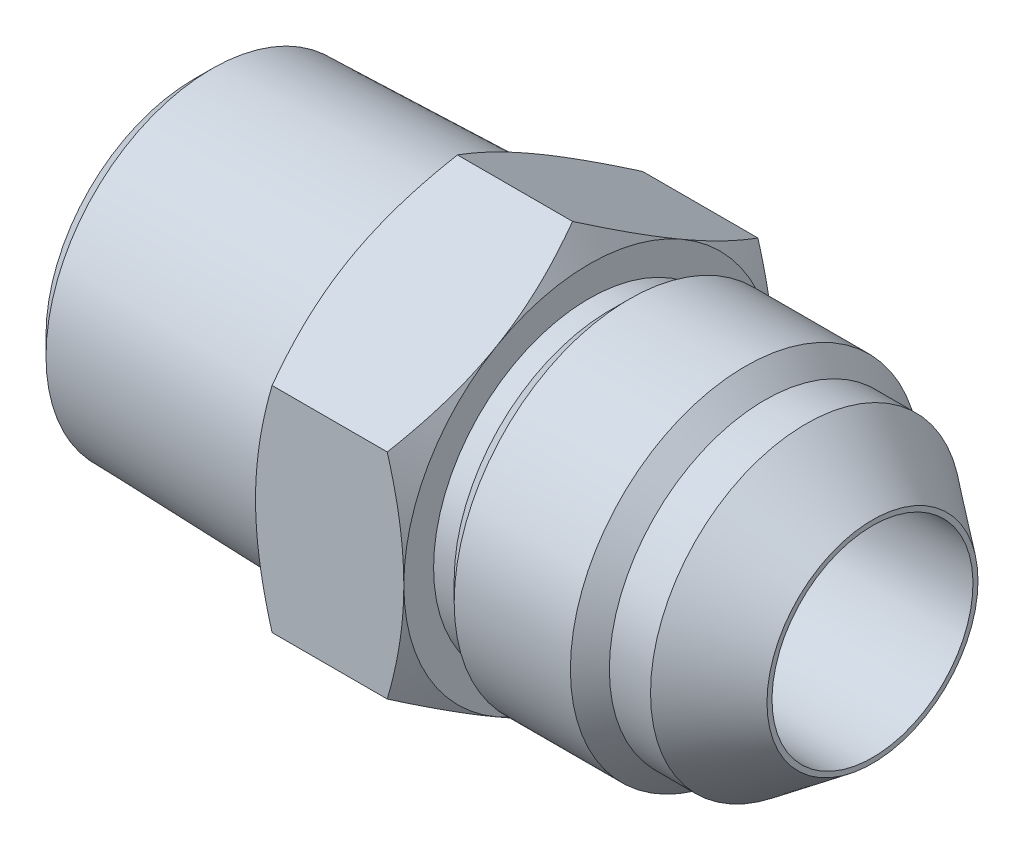
SolidWorks part; units mm, degrees
material "6061-T6 (SS)"
ref_plane "Front" through (0, 0, 0) normal (0, 0, 1) x (1, 0, 0)
ref_plane "Top" through (0, 0, 0) normal (0, 1, 0) x (1, 0, 0)
ref_plane "Right" through (0, 0, 0) normal (1, 0, 0) x (0, 0, -1)
sketch "Sketch6" plane through (0, 0, 0) normal (0, 0, 1) x (1, 0, 0)
  line L0 (-7.112, 13.335) -> (-7.112, -13.335) construction
  line L1 (26.162, 13.4937) -> (26.162, -13.4937) construction
  line L2 (-26.162, 0) -> (26.162, 0)
  line L4 (-26.162, 0) -> (-26.162, 13.4938)
  line L5 (-26.162, 13.4938) -> (26.162, 13.4937)
  line L6 (26.162, 0) -> (26.162, 13.4937)
  line L7 (-26.162, 7.747) -> (-26.162, -7.747) construction
  line L8 (-7.112, 15.0495) -> (-7.112, -15.0495) construction
  line L9 (4.318, 15.0495) -> (4.318, -15.0495) construction
  point P4 (4.318, 0)
  point P6 (-7.112, 0)
  dimension "Straight Dia" = 26.9875
  dimension "Length" = 52.324
  dimension "L1" = 21.844
  dimension "Pipe OD" = 26.67
  dimension "L2" = 19.05
  dimension "D1" = 15.494
  dimension "D2" = 30.099
revolve "Revolve3" add sketch "Sketch6" angle 360 about L2
sketch "Sketch14" plane through (26.162, 0, 0) normal (-1, 0, 0) x (0, 0, 1)
  circle A1 centre (0, 0) radius 13.4938
  circle A2 centre (0, 0) radius 13.4938
  dimension "D1" = 0
curve "Helix/Spiral1" pitch 2.1167 height 23.9607 turns 11.32 parameters "Pitch"=2.1167
sketch "Sketch15" plane through (0, 0, 0) normal (0, 0, 1) x (1, 0, 0)
  line L0 (26.162, 13.4938) -> (28.0141, 13.4938)
  line L1 (28.0141, 13.4938) -> (27.2203, 12.1189)
  line L2 (27.2203, 12.1189) -> (26.9557, 12.1189)
  line L3 (26.9557, 12.1189) -> (26.162, 13.4938)
  line L4 (27.088, 12.1189) -> (27.088, 13.4938) construction
  line L5 (26.5589, 12.8063) -> (27.6172, 12.8063) construction
  dimension "D1" = 60
  dimension "D2" = 0.2646
  dimension "D3" = 1.0583
sweep "Cut-Sweep1" [suppressed] cut profiles "Sketch15" path "Helix/Spiral1"
ref_plane "Plane1" through (-7.112, 0, 0) normal (1, 0, 0) x (0, 0, -1)
sketch "Sketch12" plane through (-7.112, 0, 0) normal (1, 0, 0) x (0, 0, -1)
  line L1 (0, 16.4978) -> (-14.2875, 8.2489)
  line L2 (-14.2875, 8.2489) -> (-14.2875, -8.2489)
  line L3 (-14.2875, -8.2489) -> (0, -16.4978)
  line L4 (0, -16.4978) -> (14.2875, -8.2489)
  line L5 (14.2875, -8.2489) -> (14.2875, 8.2489)
  line L6 (14.2875, 8.2489) -> (0, 16.4978)
  circle A0 centre (0, 0) radius 14.2875 construction
  dimension "Hex" = 28.575
extrude "Extrude1" add sketch "Sketch12" along normal up to vertex (11.43 mm away) up to point (4.318, 0, 0)
sketch "Sketch7" plane through (0, 0, 0) normal (0, 0, 1) x (1, 0, 0)
  line L0 (-26.162, 0) -> (-26.162, 7.747)
  line L2 (-26.162, 7.747) -> (26.162, 7.747)
  line L4 (26.162, 0) -> (26.162, 13.4937) construction
  line L11 (26.162, 7.747) -> (26.162, 0)
  line L12 (26.162, 0) -> (-26.162, 0)
  line L13 (-26.162, 7.747) -> (-26.162, -7.747) construction
  dimension "ID" = 15.494
sketch "Sketch10" plane through (0, 0, 0) normal (0, 0, 1) x (1, 0, 0)
  line L0 (-26.162, 13.4938) -> (26.162, 13.4937) construction
  line L1 (26.162, 13.4938) -> (28.0141, 13.4938) construction
  line L2 (-7.112, -13.335) -> (-26.162, -12.7529) construction
  line L3 (4.318, 16.4978) -> (4.318, 8.2489) construction
  line L5 (0, 0) -> (-26.162, 0) construction
  line L6 (7.4073, 13.4937) -> (4.318, 13.4937)
  line L9 (4.318, 11.9919) -> (4.318, 13.4937)
  line L21 (26.162, 13.4937) -> (16.366, 13.4937)
  line L22 (16.366, 13.4937) -> (17.8678, 11.9919)
  line L23 (17.8678, 11.9919) -> (21.0428, 11.9919)
  line L24 (21.0428, 11.9919) -> (26.162, 8.1344)
  line L25 (26.162, 8.1344) -> (26.162, 13.4937)
  line L26 (5.9055, 11.9919) -> (4.318, 11.9919)
  line L27 (7.4073, 13.4937) -> (5.9055, 11.9919)
  point P5 (13.6345, -13.4937)
  point P9 (-17.9977, -13.0024)
  dimension "D1" = 16.2687
  dimension "D2" = 37
  dimension "D3" = 3.175
  dimension "D5" = 45
  dimension "D4" = 1.5875
  dimension "D6" = 4.2333
  dimension "D7" = 0.127
  dimension "D9" = 8.1643
  dimension "D8" = 1.75
revolve "Cut-Revolve6" cut sketch "Sketch10" angle 360 about L2
revolve "Cut-Revolve5" cut sketch "Sketch7" angle 360 about L12
sketch "Sketch13" plane through (0, 0, 0) normal (0, 0, 1) x (1, 0, 0)
  line L0 (-7.112, 16.4978) -> (-7.112, 14.2875)
  line L1 (-7.112, 8.2489) -> (-7.112, 16.4978) construction
  line L2 (-7.112, 14.2875) -> (-5.8359, 16.4978)
  line L3 (-5.8359, 16.4978) -> (-7.112, 16.4978)
  line L4 (3.0419, 16.4978) -> (4.318, 14.2875)
  line L5 (4.318, 16.4978) -> (4.318, 8.2489) construction
  line L6 (4.318, 14.2875) -> (4.318, 16.4978)
  line L7 (4.318, 16.4978) -> (3.0419, 16.4978)
  dimension "D2" = 30
revolve "Cut-Revolve7" cut sketch "Sketch13" angle 360 about L2
sketch "Sketch17" plane through (-26.162, 0, 0) normal (-1, 0, 0) x (0, 0, 1)
  circle A0 centre (0, 0) radius 13.4938 construction
  circle A1 centre (0, 0) radius 13.4938
extrude "Cut-Extrude1" cut sketch "Sketch17" against normal up to vertex (19.05 mm away) up to point (-7.112, 0, 0)
ref_plane "Plane2" through (-7.112, 0, 0) normal (1, 0, 0) x (0, 0, -1)
sketch "Sketch19" plane through (-7.112, 0, 0) normal (1, 0, 0) x (0, 0, -1)
  circle A0 centre (0, 0) radius 13.335
extrude "Boss-Extrude1" add sketch "Sketch19" against normal up to vertex (19.05 mm away) draft 1.75 separate body up to point (-26.162, 0, 0)
sketch "Sketch20" plane through (-26.162, 0, 0) normal (1, 0, 0) x (0, 0, -1)
  circle A1 centre (0, 0) radius 12.753
  circle A2 centre (0, 0) radius 12.753 construction
sketch "Sketch21" plane through (0, 0, 0) normal (0, 0, 1) x (1, 0, 0)
  line L0 (-27.7682, 12.6329) -> (-26.2313, 12.6329) construction
  line L1 (-27.9069, 12.8731) -> (-26.9998, 11.3019) construction
  line L2 (-27.1199, 11.5099) -> (-26.8797, 11.5099)
  line L3 (-26.9998, 11.3019) -> (-26.0927, 12.8731) construction
  line L4 (-26.9998, 11.3019) -> (-26.8797, 11.5099) construction
  line L5 (-26.9998, 12.6329) -> (-26.9998, 12.8731) construction
  line L6 (-27.9069, 12.8731) -> (-26.0927, 12.8731) construction
  line L7 (-26.9998, 12.753) -> (-26.162, 12.753) construction
  line L8 (-26.0927, 12.8731) -> (-27.8376, 12.753)
  line L9 (-27.8376, 12.753) -> (-27.1199, 11.5099)
  line L10 (-26.8797, 11.5099) -> (-26.0927, 12.8731)
  line L11 (-26.9998, 11.3019) -> (-26.9998, 11.5099) construction
  dimension "D2" = 0.2402
  dimension "D1" = 1.8143
curve "Helix/Spiral2" [suppressed] parameters "Pitch"=1.8143
chamfer "Chamfer1" distance 1.3607 angle 45 1 edges at (-26.162, 0, -12.753) first distance on face at (-26.162, 0, -12.753)
sketch "Sketch22" plane through (-7.112, 0, 0) normal (1, 0, 0) x (0, 0, -1)
  circle A1 centre (0, 0) radius 13.335
  circle A2 centre (0, 0) radius 13.335
  dimension "D1" = 0
sweep "Cut-Sweep2" [suppressed] cut profiles "Sketch21" path "Helix/Spiral2"
extrude "Boss-Extrude3" add sketch "Sketch22" against normal up to vertex (19.05 mm away) draft 15 up to point (-26.162, 13.4938, 0)
combine bodies "Combine1" operation type add bodies to combine 173 169
sketch "Sketch23" plane through (-26.162, 0, 0) normal (-1, 0, 0) x (0, 0, 1)
  circle A2 centre (0, 0) radius 7.747
extrude "Cut-Extrude2" cut sketch "Sketch23" against normal up to vertex (19.05 mm away) up to point (-7.112, 0, 0)
equation "\"D3@Helix/Spiral1\" = \"L1@Sketch6\"+\"Pitch@Helix/Spiral1\""
equation "\"D2@Sketch15\" = \"Pitch@Helix/Spiral1\"*.125"
equation "\"D3@Sketch15\" = \"Pitch@Helix/Spiral1\"*.5"
equation "\"D3@Sketch10\" = \"Pitch@Helix/Spiral1\"*1.5"
equation "\"D1@Sketch10\" = \"ID@Sketch7\"*1.05"
equation "\"D1@Sketch21\" = \"Pitch@Helix/Spiral2\""
equation "\"D3@Helix/Spiral2\" = \"L2@Sketch6\"+\"Pitch@Helix/Spiral2\""
equation "\"D1@Chamfer1\" = \"Pitch@Helix/Spiral2\"*.75"
equation "\"D4@Sketch10\" = \"Pitch@Helix/Spiral1\"*.75"
equation "\"D6@Sketch10\" = \"Pitch@Helix/Spiral1\"*2"
equation "\"D9@Sketch10\" = \"Pitch@Helix/Spiral2\"*4.5"
equation "\"D2@Sketch6\" = \"Hex@Sketch12\"+.06"
